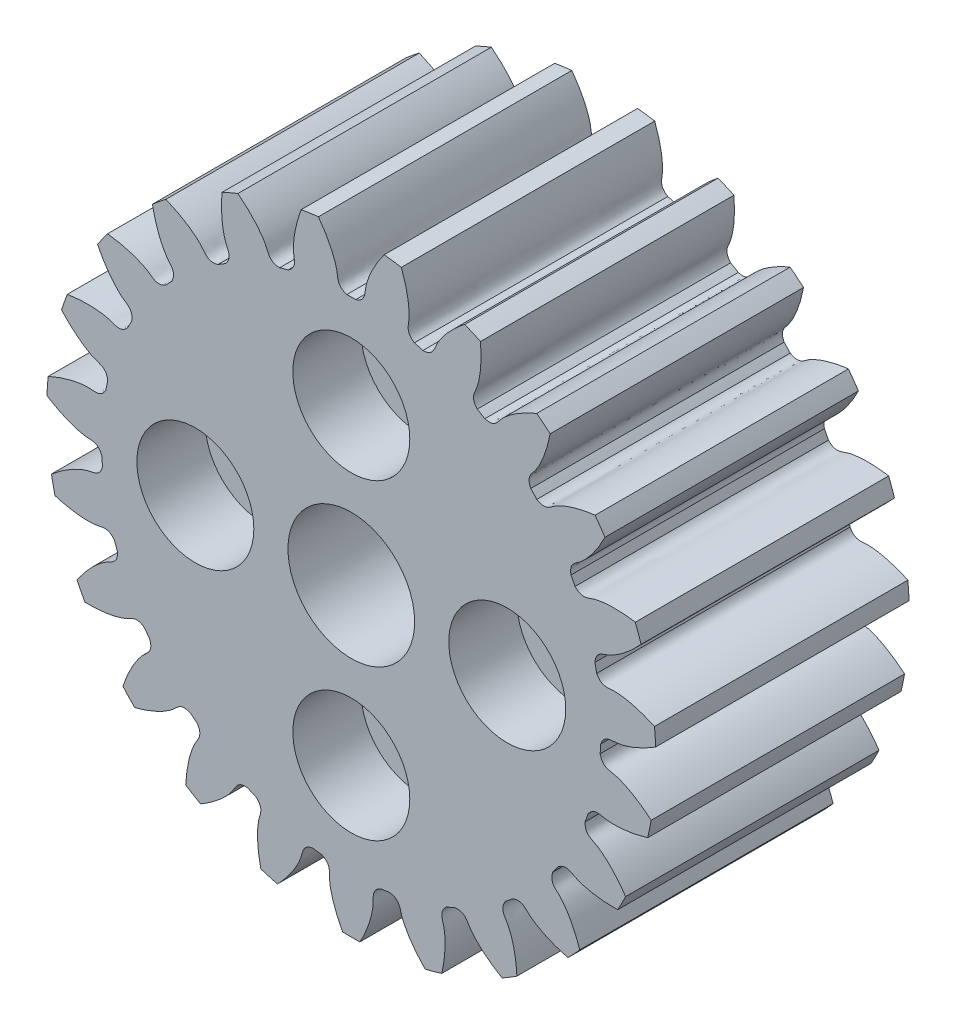
SolidWorks part; units mm, degrees
ref_plane "前视基准面" through (0, 0, 0) normal (0, 0, 1) x (1, 0, 0)
ref_plane "上视基准面" through (0, 0, 0) normal (0, 1, 0) x (1, 0, 0)
ref_plane "右视基准面" through (0, 0, 0) normal (1, 0, 0) x (0, 0, -1)
sketch "草图1" plane through (0, 0, 0) normal (0, 0, 1) x (1, 0, 0)
  circle A0 centre (0, 0) radius 15.625
extrude "凸台-拉伸1" add sketch "草图1" along normal blind 13
ref_axis "基准轴1" through (0, 0, -0.65) along (0, 0, 1)
sketch "草图2" plane through (0, 0, 0) normal (0, 0, 1) x (1, 0, 0)
  line L0 (0, 0) -> (0, 15.625) construction
  circle A0 centre (0, 0) radius 15.625 construction
  arc A1 (0.2267, 12.8105) -> (-0.2267, 12.8105) centre (0, 0) ccw
  arc A2 (3.9771, 17.7327) -> (-3.9771, 17.7327) centre (0, 0) ccw
  spline S0 degree 3 poles (0.2267, 12.8105) (0.7222, 12.9585) (0.6797, 13.2923) (0.7412, 13.6215) (0.7494, 13.6612) (0.7596, 13.7059) (0.772, 13.7558) (0.7868, 13.8105) (0.8042, 13.8702) (0.8244, 13.9346) (0.8476, 14.0038) (0.874, 14.0775) (0.9038, 14.1558) (0.9372, 14.2385) (0.9743, 14.3255) (1.0154, 14.4166) (1.0607, 14.5117) (1.1102, 14.6108) (1.1642, 14.7137) (1.2229, 14.8201) (1.2864, 14.9301) (1.3549, 15.0434) (1.4285, 15.1599) (1.5074, 15.2794) (1.5918, 15.4017) (1.6817, 15.5267) (1.7774, 15.6542) (1.8789, 15.7841) (1.9864, 15.916) (2.1, 16.0499) (2.2198, 16.1856) (2.346, 16.3228) (2.4787, 16.4614) (2.6179, 16.6011) (2.7638, 16.7418) (2.9164, 16.8831) (3.0758, 17.025) (3.2422, 17.1672) (3.4155, 17.3095) (3.6589, 17.5012) (3.8479, 17.641) (3.9771, 17.7327) knots 0 0 0 0 0.147387 0.15296 0.159389 0.166677 0.174821 0.183823 0.193683 0.204399 0.215973 0.228404 0.241693 0.255839 0.270842 0.286703 0.303421 0.320996 0.339428 0.358718 0.378866 0.39987 0.421732 0.444451 0.468028 0.492462 0.517753 0.543901 0.570907 0.59877 0.627491 0.657069 0.687504 0.718796 0.750946 0.783953 0.817818 0.85254 0.888119 0.924555 1 1 1 1
  spline S1 degree 3 poles (-0.2267, 12.8105) (-0.7222, 12.9585) (-0.6797, 13.2923) (-0.7412, 13.6215) (-0.7494, 13.6612) (-0.7596, 13.7059) (-0.772, 13.7558) (-0.7868, 13.8105) (-0.8042, 13.8702) (-0.8244, 13.9346) (-0.8476, 14.0038) (-0.874, 14.0775) (-0.9038, 14.1558) (-0.9372, 14.2385) (-0.9743, 14.3255) (-1.0154, 14.4166) (-1.0607, 14.5117) (-1.1102, 14.6108) (-1.1642, 14.7137) (-1.2229, 14.8201) (-1.2864, 14.9301) (-1.3549, 15.0434) (-1.4285, 15.1599) (-1.5074, 15.2794) (-1.5918, 15.4017) (-1.6817, 15.5267) (-1.7774, 15.6542) (-1.8789, 15.7841) (-1.9864, 15.916) (-2.1, 16.0499) (-2.2198, 16.1856) (-2.346, 16.3228) (-2.4787, 16.4614) (-2.6179, 16.6011) (-2.7638, 16.7418) (-2.9164, 16.8831) (-3.0758, 17.025) (-3.2422, 17.1672) (-3.4155, 17.3095) (-3.6589, 17.5012) (-3.8479, 17.641) (-3.9771, 17.7327) knots 0 0 0 0 0.147387 0.15296 0.159389 0.166677 0.174821 0.183823 0.193683 0.204399 0.215973 0.228404 0.241693 0.255839 0.270842 0.286703 0.303421 0.320996 0.339428 0.358718 0.378866 0.39987 0.421732 0.444451 0.468028 0.492462 0.517753 0.543901 0.570907 0.59877 0.627491 0.657069 0.687504 0.718796 0.750946 0.783953 0.817818 0.85254 0.888119 0.924555 1 1 1 1
extrude "切除-拉伸1" cut sketch "草图2" along normal through all
pattern_circular "阵列(圆周)1" count 23 every 15.652 about axis through (0, 0, -0.65) along (0, 0, 1) of "切除-拉伸1"
sketch "草图3" plane through (0, 0, 0) normal (0, 0, 1) x (1, 0, 0)
  circle A0 centre (0, 0) radius 14.375 construction
  dimension "Dn" = 28.75
sketch "草图4" plane through (0, 0, 13) normal (0, 0, 1) x (1, 0, 0)
  circle A0 centre (0, 0) radius 3.25
  circle A1 centre (0, 0) radius 8 construction
  circle A2 centre (0, 8) radius 1.6
  circle A3 centre (8, 0) radius 1.6
  circle A4 centre (0, -8) radius 1.6
  circle A5 centre (-8, 0) radius 1.6
  point P15 (0, 0)
  dimension "D1" = 6.5
  dimension "D2" = 16
  dimension "D3" = 3.2
  dimension "D4" = 4
extrude "切除-拉伸2" cut sketch "草图4" against normal through all
sketch "草图5" plane through (0, 0, 13) normal (0, 0, 1) x (1, 0, 0)
  circle A0 centre (0, 8) radius 3
  circle A1 centre (8, 0) radius 3
  circle A2 centre (0, -8) radius 3
  circle A3 centre (-8, 0) radius 3
  point P12 (0, 0)
  dimension "D1" = 6
  dimension "D2" = 4
extrude "切除-拉伸3" cut sketch "草图5" against normal blind 3.5
sketch "草图6" plane through (0, 0, 0) normal (0, 0, -1) x (-1, 0, 0)
  circle A0 centre (0, 0) radius 12.4
  dimension "D1" = 24.8
